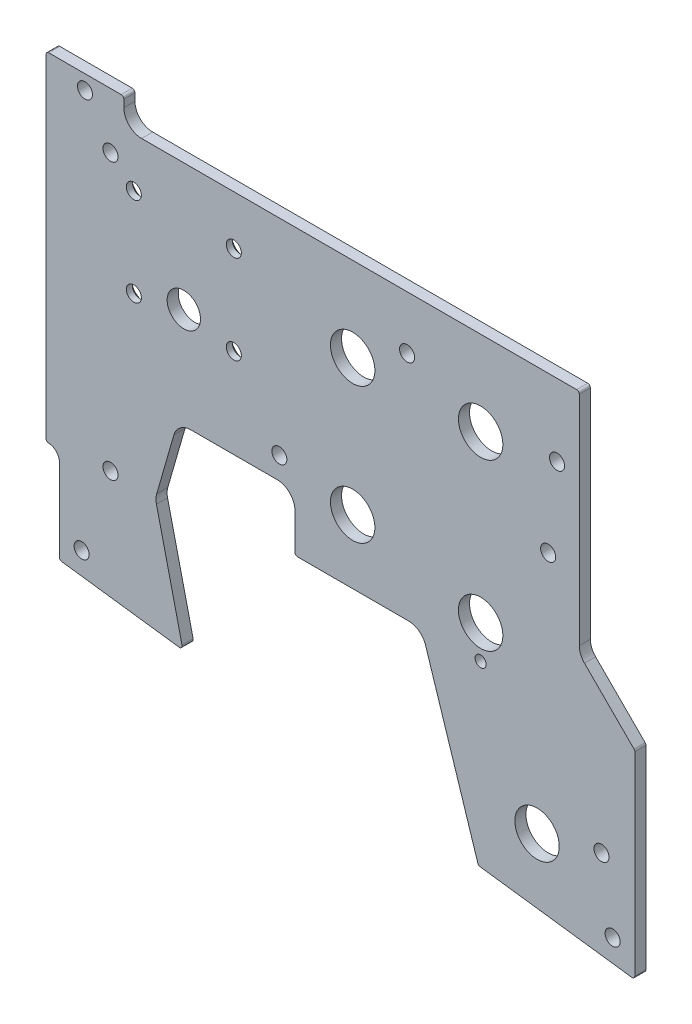
SolidWorks part; units mm, degrees
ref_plane "Front Plane" through (0, 0, 0) normal (0, 0, 1) x (1, 0, 0)
ref_plane "Top Plane" through (0, 0, 0) normal (0, 1, 0) x (1, 0, 0)
ref_plane "Right Plane" through (0, 0, 0) normal (1, 0, 0) x (0, 0, -1)
sketch "Sketch1" plane through (0, 0, 0) normal (0, 0, 1) x (1, 0, 0)
  line L16 (3.81, -91.8845) -> (3.81, -115.4033)
  line L17 (4.4725, -116.1588) -> (38.0231, -120.5758)
  line L18 (38.8645, -119.6465) -> (31.5446, -88.4134)
  line L19 (31.6093, -85.8475) -> (36.5334, -68.7608)
  line L20 (41.4148, -65.0875) -> (66.04, -65.0875)
  line L21 (71.12, -70.1675) -> (71.12, -80.518)
  line L22 (71.882, -81.28) -> (103.6122, -81.28)
  line L23 (108.4484, -84.805) -> (123.4233, -131.3792)
  line L24 (124.0493, -131.9014) -> (167.4135, -137.6104)
  line L25 (168.275, -136.8549) -> (168.275, -81.3036)
  line L26 (168.0518, -80.7647) -> (153.8879, -66.6008)
  line L27 (152.4, -63.0087) -> (152.4, -0.762)
  line L28 (151.638, 0) -> (27.305, 0)
  line L29 (22.225, 5.08) -> (22.225, 7.1755)
  line L30 (21.463, 7.9375) -> (0.762, 7.9375)
  line L31 (0, 7.1755) -> (0, -87.9495)
  line L32 (3.81, -91.8845) -> (3.81, -115.4033)
  line L33 (4.4725, -116.1588) -> (38.0231, -120.5758)
  line L34 (38.8645, -119.6465) -> (31.5446, -88.4134)
  line L35 (31.6093, -85.8475) -> (36.5334, -68.7608)
  line L36 (41.4148, -65.0875) -> (66.04, -65.0875)
  line L37 (71.12, -70.1675) -> (71.12, -80.518)
  line L38 (71.882, -81.28) -> (103.6122, -81.28)
  line L39 (108.4484, -84.805) -> (123.4233, -131.3792)
  line L40 (124.0493, -131.9014) -> (167.4135, -137.6104)
  line L41 (168.275, -136.8549) -> (168.275, -81.3036)
  line L42 (168.0518, -80.7647) -> (153.8879, -66.6008)
  line L43 (152.4, -63.0087) -> (152.4, -0.762)
  line L44 (151.638, 0) -> (27.305, 0)
  line L45 (22.225, 5.08) -> (22.225, 7.1755)
  line L46 (21.463, 7.9375) -> (0.762, 7.9375)
  line L47 (0, 7.1755) -> (0, -87.9495)
  arc A17 (3.81, -91.8845) -> (0.7374, -88.7112) centre (0.635, -91.8845) ccw
  arc A18 (3.81, -115.4033) -> (4.4725, -116.1588) centre (4.572, -115.4033) ccw
  arc A19 (38.0231, -120.5758) -> (38.8645, -119.6465) centre (38.1226, -119.8204) ccw
  arc A20 (31.6093, -85.8475) -> (31.5446, -88.4134) centre (36.4906, -87.2542) ccw
  arc A21 (41.4148, -65.0875) -> (36.5334, -68.7608) centre (41.4148, -70.1675) ccw
  arc A22 (71.12, -70.1675) -> (66.04, -65.0875) centre (66.04, -70.1675) ccw
  arc A23 (71.12, -80.518) -> (71.882, -81.28) centre (71.882, -80.518) ccw
  arc A24 (108.4484, -84.805) -> (103.6122, -81.28) centre (103.6122, -86.36) ccw
  arc A25 (123.4233, -131.3792) -> (124.0493, -131.9014) centre (124.1487, -131.1459) ccw
  arc A26 (167.4135, -137.6104) -> (168.275, -136.8549) centre (167.513, -136.8549) ccw
  arc A27 (168.275, -81.3036) -> (168.0518, -80.7647) centre (167.513, -81.3036) ccw
  arc A28 (152.4, -63.0087) -> (153.8879, -66.6008) centre (157.48, -63.0087) ccw
  arc A29 (152.4, -0.762) -> (151.638, 0) centre (151.638, -0.762) ccw
  arc A30 (22.225, 5.08) -> (27.305, 0) centre (27.305, 5.08) ccw
  arc A31 (22.225, 7.1755) -> (21.463, 7.9375) centre (21.463, 7.1755) ccw
  arc A32 (0.762, 7.9375) -> (0, 7.1755) centre (0.762, 7.1755) ccw
  arc A33 (0, -87.9495) -> (0.7374, -88.7112) centre (0.762, -87.9495) ccw
  arc A34 (3.81, -91.8845) -> (0.7374, -88.7112) centre (0.635, -91.8845) ccw
  arc A35 (3.81, -115.4033) -> (4.4725, -116.1588) centre (4.572, -115.4033) ccw
  arc A36 (38.0231, -120.5758) -> (38.8645, -119.6465) centre (38.1226, -119.8204) ccw
  arc A37 (31.6093, -85.8475) -> (31.5446, -88.4134) centre (36.4906, -87.2542) ccw
  arc A38 (41.4148, -65.0875) -> (36.5334, -68.7608) centre (41.4148, -70.1675) ccw
  arc A39 (71.12, -70.1675) -> (66.04, -65.0875) centre (66.04, -70.1675) ccw
  arc A40 (71.12, -80.518) -> (71.882, -81.28) centre (71.882, -80.518) ccw
  arc A41 (108.4484, -84.805) -> (103.6122, -81.28) centre (103.6122, -86.36) ccw
  arc A42 (123.4233, -131.3792) -> (124.0493, -131.9014) centre (124.1487, -131.1459) ccw
  arc A43 (167.4135, -137.6104) -> (168.275, -136.8549) centre (167.513, -136.8549) ccw
  arc A44 (168.275, -81.3036) -> (168.0518, -80.7647) centre (167.513, -81.3036) ccw
  arc A45 (152.4, -63.0087) -> (153.8879, -66.6008) centre (157.48, -63.0087) ccw
  arc A46 (152.4, -0.762) -> (151.638, 0) centre (151.638, -0.762) ccw
  arc A47 (22.225, 5.08) -> (27.305, 0) centre (27.305, 5.08) ccw
  arc A48 (22.225, 7.1755) -> (21.463, 7.9375) centre (21.463, 7.1755) ccw
  arc A49 (0.762, 7.9375) -> (0, 7.1755) centre (0.762, 7.1755) ccw
  arc A50 (0, -87.9495) -> (0.7374, -88.7112) centre (0.762, -87.9495) ccw
  dimension "D1" = 0
extrude "Boss-Extrude1" add sketch "Sketch1" against normal blind 3.175
hole_wizard "#6 Clearance Hole1" positions "Sketch3" profile "Sketch2" hole size "#6" standard "ANSI Inch" end condition through all
sketch "Sketch3" plane through (0, 0, -3.175) normal (0, 0, -1) x (-1, 0, 0)
  point P0 (-11.1125, 3.81)
  point P3 (-18.415, -7.9375)
  point P6 (-103.1875, -15.24)
  point P9 (-143.51, -44.45)
  point P12 (-158.75, -111.125)
  point P15 (-18.415, -86.741)
  point P18 (-66.675, -58.7375)
  point P21 (-10.16, -110.5028)
  point P25 (-146.05, -20.6375)
  point P28 (-161.925, -130.483)
sketch "Sketch2" plane through (11.1125, 3.81, -3.175) normal (1, 0, 0) x (0, 1, 0)
  line L0 (0, 0) -> (0, 3.175)
  line L1 (0, 3.175) -> (2.1526, 3.175)
  line L2 (2.1526, 3.175) -> (2.1526, 0)
  line L5 (2.1526, 0) -> (0, 0)
  line L11 (0, -6.35) -> (0, 107.95) construction
  dimension "Thru Hole Dia." = 4.3053
  dimension "Thru Hole Depth" = 3.175
sketch "Sketch4" plane through (0, 0, -3.175) normal (0, 0, -1) x (-1, 0, 0)
  circle A0 centre (-140.335, -115.57) radius 6.35
  circle A1 centre (-124.206, -71.4375) radius 6.35
  circle A2 centre (-87.63, -62.992) radius 6.35
  circle A3 centre (-87.63, -24.13) radius 6.35
  circle A4 centre (-124.206, -24.13) radius 6.35
  circle A5 centre (-124.206, -80.9625) radius 1.5875
  circle A6 centre (-39.37, -36.322) radius 4.7625
  dimension "D1" = 12.7
  dimension "D2" = 3.175
  dimension "D4" = 9.525
  dimension "D3" = 9.525
extrude "Cut-Extrude1" cut sketch "Sketch4" against normal through all
hole_wizard "CSK for #6 Flat Head Machine Screw (100)1" positions "Sketch6" profile "Sketch5" countersink size "#6" standard "ANSI Inch" end condition through all
sketch "Sketch6" plane through (0, 0, -3.175) normal (0, 0, -1) x (-1, 0, 0)
  point P0 (-53.6575, -14.097)
  point P2 (-25.0825, -14.097)
  point P4 (-25.0825, -39.497)
  point P6 (-53.6575, -39.497)
sketch "Sketch5" plane through (53.6575, -14.097, -3.175) normal (1, 0, 0) x (0, 1, 0)
  line L0 (0, 0) -> (0, 3.175)
  line L1 (0, 3.175) -> (2.1526, 3.175)
  line L2 (2.1526, 3.175) -> (2.1526, 1.4209)
  line L3 (2.1526, 1.4209) -> (3.846, 0)
  line L5 (3.846, 0) -> (0, 0)
  line L6 (-2.1526, 1.4209) -> (-3.846, 0) construction
  line L11 (0, -6.35) -> (0, 107.95) construction
  dimension "Thru Hole Dia." = 4.3053
  dimension "Thru Hole Depth" = 3.175
  dimension "Near C'Sink Dia." = 7.692
  dimension "Near C'Sink Angle" = 100
